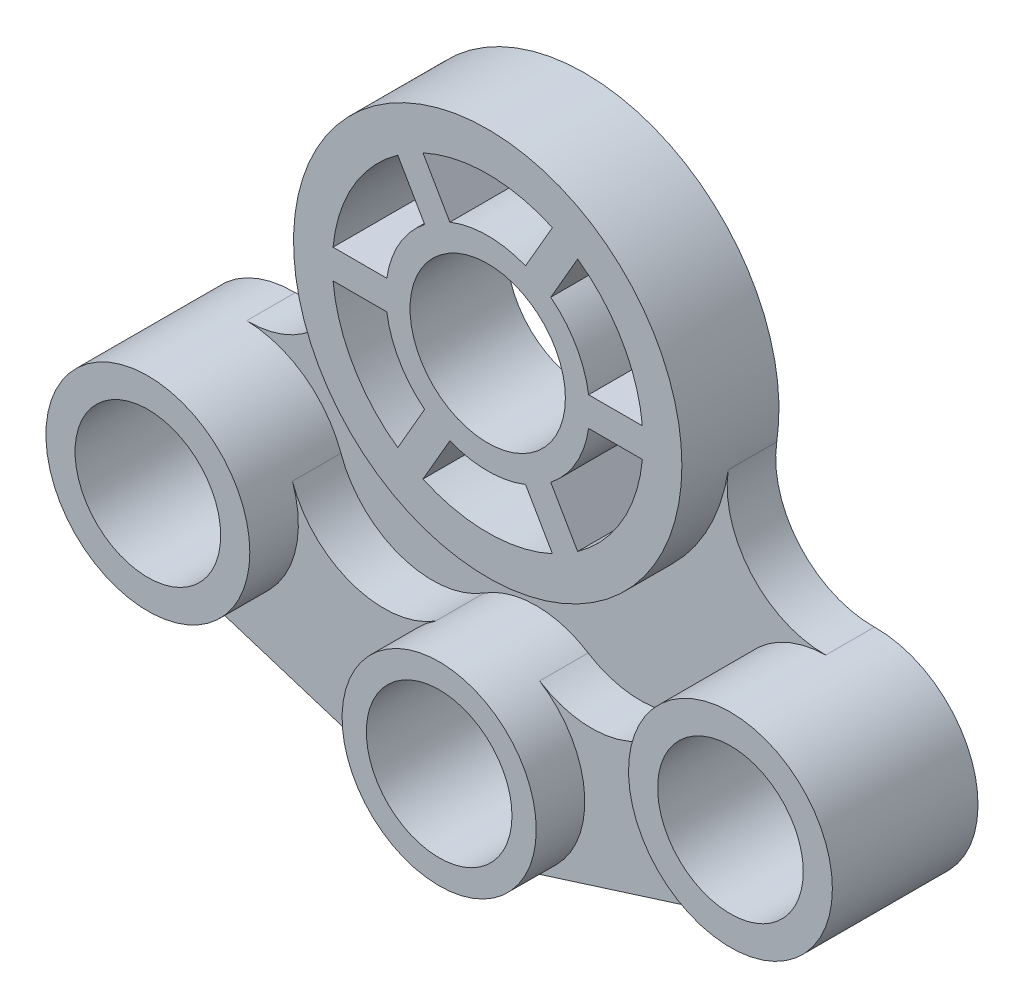
SolidWorks part; units mm, degrees
material "6061-T6 (SS)"
ref_plane "Front Plane" through (0, 0, 0) normal (0, 0, 1) x (1, 0, 0)
ref_plane "Top Plane" through (0, 0, 0) normal (0, 1, 0) x (1, 0, 0)
ref_plane "Right Plane" through (0, 0, 0) normal (1, 0, 0) x (0, 0, -1)
sketch "Sketch3" plane through (0, 0, 0) normal (0, 0, 1) x (1, 0, 0)
  line L0 (20.7846, 3) -> (31.8591, 3)
  line L1 (20.7846, -3) -> (31.8591, -3)
  line L2 (12.9904, -16.5) -> (18.5276, -26.0908)
  line L3 (7.7942, -19.5) -> (13.3315, -29.0908)
  line L4 (-7.7942, -19.5) -> (-13.3315, -29.0908)
  line L5 (-12.9904, -16.5) -> (-18.5276, -26.0908)
  line L6 (-20.7846, -3) -> (-31.8591, -3)
  line L7 (-20.7846, 3) -> (-31.8591, 3)
  line L8 (-12.9904, 16.5) -> (-18.5276, 26.0908)
  line L9 (-7.7942, 19.5) -> (-13.3315, 29.0908)
  line L10 (7.7942, 19.5) -> (13.3315, 29.0908)
  line L11 (12.9904, 16.5) -> (18.5276, 26.0908)
  line L12 (66.325, -70.0249) -> (6.0238, -89.0713)
  line L13 (0, -55) -> (0, 55) construction
  line L14 (-66.325, -70.0249) -> (-6.0238, -89.0713)
  arc A0 (-18.5276, 26.0908) -> (-31.8591, 3) centre (0, 0) ccw
  circle A1 centre (0, 0) radius 16
  arc A2 (-12.9904, 16.5) -> (-20.7846, 3) centre (0, 0) ccw
  circle A3 centre (0, 0) radius 40
  arc A4 (7.7942, 19.5) -> (-7.7942, 19.5) centre (0, 0) ccw
  arc A5 (13.3315, 29.0908) -> (-13.3315, 29.0908) centre (0, 0) ccw
  arc A6 (20.7846, 3) -> (12.9904, 16.5) centre (0, 0) ccw
  arc A7 (31.8591, 3) -> (18.5276, 26.0908) centre (0, 0) ccw
  arc A8 (12.9904, -16.5) -> (20.7846, -3) centre (0, 0) ccw
  arc A9 (18.5276, -26.0908) -> (31.8591, -3) centre (0, 0) ccw
  arc A10 (-7.7942, -19.5) -> (7.7942, -19.5) centre (0, 0) ccw
  arc A11 (-13.3315, -29.0908) -> (13.3315, -29.0908) centre (0, 0) ccw
  arc A12 (-31.8591, -3) -> (-18.5276, -26.0908) centre (0, 0) ccw
  arc A13 (-20.7846, -3) -> (-12.9904, -16.5) centre (0, 0) ccw
  arc A14 (39.5469, -6.0038) -> (59.6519, -29.0029) centre (59.3203, -9.0056) ccw
  circle A15 centre (60, -50) radius 21
  circle A16 centre (60, -50) radius 15
  circle A17 centre (0, -70) radius 20
  arc A18 (40.2251, -42.9321) -> (10.696, -53.1004) centre (21.3919, -36.2008) cw
  circle A19 centre (0, -70) radius 15
  arc A20 (-39.5469, -6.0038) -> (-59.6519, -29.0029) centre (-59.3203, -9.0056) cw
  arc A21 (-40.2251, -42.9321) -> (-10.696, -53.1004) centre (-21.3919, -36.2008) ccw
  circle A22 centre (-60, -50) radius 15
  circle A23 centre (-60, -50) radius 21
  dimension "D4" = 21
  dimension "D5" = 32
  dimension "D6" = 80
  dimension "D7" = 42
  dimension "32" = 32
  dimension "D8" = 30
  dimension "D9" = 20
  dimension "D10" = 40
  dimension "D14" = 20
  dimension "D1" = 3
  dimension "D2" = 6
  dimension "D11" = 20
  dimension "D12" = 60
  dimension "D13" = 50
  dimension "D3" = 6
extrude "Boss-Extrude1" add sketch "Sketch3" along normal blind 20 contours A3 A11 L4 A10 L3 A9 L2 A8 L1 A7 L0 A6 L11 A5 L10 A4 L9 L8 A2 L7 A0 A1 L6 A13 L5 A12 | A21 A23 L14 A17 | A15 A18 A17 L12 region at (32.3694, -68.4418, 0) region at (-32.3694, -68.4418, 0) region at (0, -38.8686, 0)
extrude "Boss-Extrude2" add sketch "Sketch3<3>" along normal blind 10 contours A20 A23 A21 A17 A18 A15 A14 A3 region at (27.4822, -53.8873, 0)
sketch "Sketch3<3>" plane through (0, 0, 0) normal (0, 0, 1) x (1, 0, 0) same geometry as "Sketch3"
extrude "Boss-Extrude3" add sketch "Sketch3<4>" along normal blind 30 contours A17 A19 | A23 A22 | A15 A16 region at (45.304, -64.1574, 0) region at (0, -89.4343, 0) region at (-80.1413, -46.7236, 0)
sketch "Sketch3<4>" plane through (0, 0, 0) normal (0, 0, 1) x (1, 0, 0) same geometry as "Sketch3"
